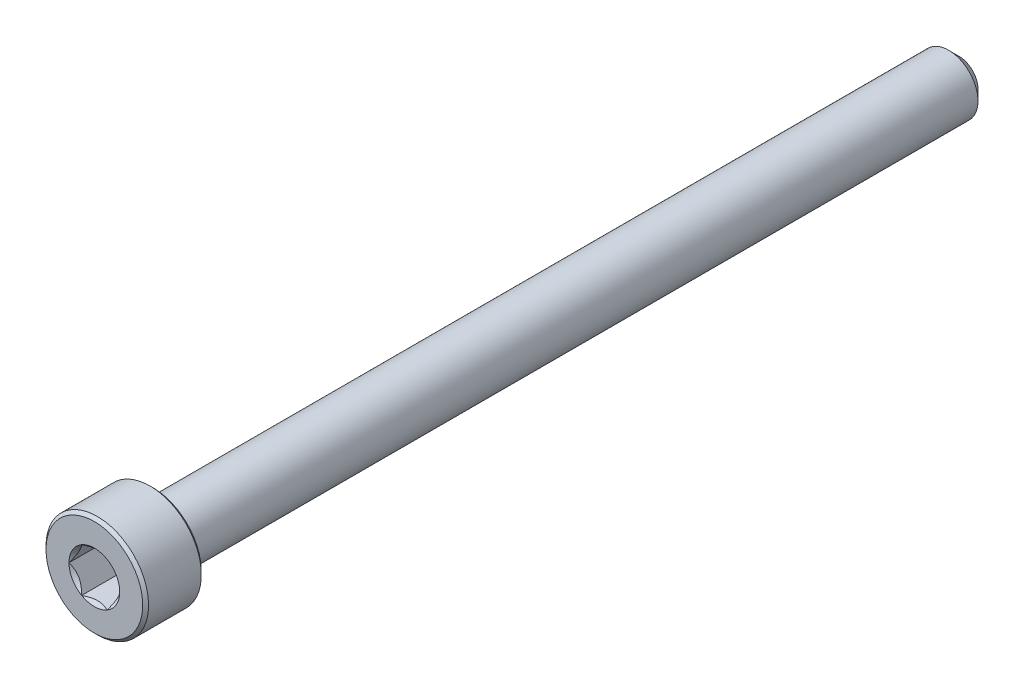
SolidWorks part; units mm, degrees
ref_plane "Front Plane" through (0, 0, 0) normal (0, 0, 1) x (1, 0, 0)
ref_plane "Top Plane" through (0, 0, 0) normal (0, 1, 0) x (1, 0, 0)
ref_plane "Right Plane" through (0, 0, 0) normal (1, 0, 0) x (0, 0, -1)
sketch "Sketch1" plane through (0, 0, 0) normal (1, 0, 0) x (0, 0, -1)
  line L0 (-29.5, 0) -> (29.5, 0) construction
  line L1 (29.5, 0) -> (29.5, 1.3) construction
  line L2 (29.5, 1.3) -> (28.8, 2) construction
  line L3 (28.8, 2) -> (9.5, 2) construction
  line L4 (9.5, 2) -> (-25.5, 2) construction
  line L5 (-25.5, 2) -> (-25.5, 3.5) construction
  line L6 (-25.5, 3.5) -> (-29.5, 3.5) construction
  line L7 (-29.5, 3.5) -> (-29.5, 0) construction
  line L8 (29.5, 1.3) -> (29.5, 2) construction
  line L9 (29.4563, 2.0758) -> (29.8063, 1.4696) construction
  line L10 (29.8063, 1.4696) -> (30.1563, 2.0758) construction
  line L11 (30.1563, 2.0758) -> (29.4563, 2.0758) construction
  line L12 (29.8063, 2.0758) -> (29.8063, 2) construction
  line L13 (29.8063, 1.4696) -> (29.8063, 1.5453) construction
  line L14 (29.7625, 1.5453) -> (29.85, 1.5453) construction
  line L15 (29.5, 2) -> (30.1125, 2) construction
  line L16 (29.4781, 2.0379) -> (30.1344, 2.0379) construction
  line L17 (29.5, 0) -> (29.5, -2) construction
  line L18 (-25.7, 3.5) -> (-25.5, 3.3) construction
  line L19 (-29.3, 3.5) -> (-29.5, 3.3) construction
  point P0 (-29.5, 1.5)
  point P3 (27.05, 2)
  point P4 (0, 0)
  point P18 (8.5, 2)
  point P22 (29.8063, 1.5453)
  point P24 (9.5, 2)
  point P25 (29.8063, 2)
  point P28 (29.8063, 2.0379)
  point P29 (27.05, -2)
  point P30 (-24.5, 2)
  point P31 (-27.5, 3.5)
  point P37 (-26.2, 3.5)
  point P38 (-29.2, 3.5)
  dimension "head height" = 4
  dimension "threaded length" = 20
  dimension "D1" = 45
  dimension "head dia" = 7
  dimension "thread dia" = 4
  dimension "drive size" = 3
  dimension "pitch" = 0.7
  dimension "D2" = 0.0875
  dimension "D3" = 0.7
  dimension "D4" = 2.45
  dimension "D5" = 1
  dimension "D6" = 1
  dimension "D7" = 0.2
  dimension "D8" = 0.2
  dimension "D9" = 0.2
  dimension "D10" = 0.1
  dimension "D11" = 0.5
  dimension "length" = 55
sketch "Sketch2" plane through (0, 0, 0) normal (1, 0, 0) x (0, 0, -1)
  line L0 (-29.5, 0) -> (-29.5, 3.3)
  line L1 (-29.3, 3.5) -> (-25.7, 3.5)
  line L2 (-25.5, 3.3) -> (-25.5, 2)
  line L3 (-25.5, 2) -> (28.8, 2)
  line L4 (28.8, 2) -> (29.5, 1.3)
  line L5 (29.5, 1.3) -> (29.5, 0)
  line L6 (-25.7, 3.5) -> (-25.5, 3.3) construction
  line L7 (29.5, 0) -> (-29.5, 0)
  line L8 (-29.3, 3.5) -> (-29.5, 3.3) construction
  line L9 (-25.7, 3.5) -> (-25.5, 3.3)
  line L10 (-29.3, 3.5) -> (-29.5, 3.3)
revolve "Revolve1" add sketch "Sketch2" angle 360 about L7
sketch "Sketch3" plane through (0, 0, 29.5) normal (0, 0, 1) x (1, 0, 0)
  line L1 (0.866, 1.5) -> (-0.866, 1.5)
  line L2 (-0.866, 1.5) -> (-1.7321, 0)
  line L3 (-1.7321, 0) -> (-0.866, -1.5)
  line L4 (-0.866, -1.5) -> (0.866, -1.5)
  line L5 (0.866, -1.5) -> (1.7321, 0)
  line L6 (1.7321, 0) -> (0.866, 1.5)
  circle A0 centre (0, 0) radius 1.5 construction
extrude "Cut-Extrude1" cut sketch "Sketch3" against normal offset from surface (3 mm away) 1 up to face at (-3.3, 0, 25.5)
sketch "Sketch4" plane through (0, 0, 29.5) normal (0, 0, 1) x (1, 0, 0)
  circle A0 centre (0, 0) radius 1.7321
extrude "Cut-Extrude2" cut sketch "Sketch4" against normal up to vertex (2 mm away) draft 45 up to point (0, 3.5, 27.5)
ref_plane "Plane1" [suppressed] through (0, 0, -9.5) normal (0, 0, 1) x (1, 0, 0)
split "Split1" [suppressed] bodies to split 106
sketch "Sketch6" [suppressed] plane through (0, 0, -29.5) normal (0, 0, -1) x (-1, 0, 0)
  circle A0 centre (0, 0) radius 2
curve "Helix/Spiral1" [suppressed] pitch 0.7 height 20.7 turns 29.5714
sketch "Sketch7" [suppressed] plane through (0, 0, 0) normal (1, 0, 0) x (0, 0, -1)
  line L0 (29.4781, 2.0379) -> (30.1344, 2.0379)
  line L1 (30.1344, 2.0379) -> (29.85, 1.5453)
  line L2 (29.85, 1.5453) -> (29.7625, 1.5453)
  line L3 (29.7625, 1.5453) -> (29.4781, 2.0379)
sweep "Cut-Sweep1" [suppressed] cut profiles "Sketch7" path "Helix/Spiral1"
sketch "Sketch8" [suppressed] plane through (0, 0, -9.5) normal (0, 0, -1) x (-1, 0, 0)
  circle A0 centre (0, 0) radius 2
extrude "Boss-Extrude1" [suppressed] add sketch "Sketch8" along normal through all draft 45
ref_plane "Plane2" [suppressed] through (0, 0, 27.5) normal (0, 0, 1) x (1, 0, 0)
sketch "Sketch9" [suppressed] plane through (0, 0, 27.5) normal (0, 0, 1) x (1, 0, 0)
  line L0 (0, 3.325) -> (0.0611, 3.4995)
  line L1 (0, 3.325) -> (-0.0611, 3.4995)
  line L2 (0, 3.5) -> (0, 0) construction
  line L3 (-0.0611, 3.4995) -> (0, 0) construction
  line L4 (0, 0) -> (0.0611, 3.4995) construction
  arc A0 (0.0611, 3.4995) -> (-0.0611, 3.4995) centre (0, 0) ccw
  circle A1 centre (0, 0) radius 3.325 construction
  dimension "D2" = 6.65
  dimension "D3" = 2
extrude "Cut-Extrude4" [suppressed] cut sketch "Sketch9" against normal up to vertex and the other way up to vertex
pattern_circular "CirPattern2" [suppressed] count 175 over 360 about axis through (0, 0, 29.5) along (0, 0, -1) of bodies 113
equation "\"D2@Sketch1\"=\"pitch@Sketch1\"/8"
equation "\"D3@Sketch1\"=\"pitch@Sketch1\""
equation "\"D3@Helix/Spiral1\"=\"threaded length@Sketch1\"+\"pitch@Sketch1\""
equation "\"D4@Helix/Spiral1\"=\"pitch@Sketch1\""
equation "\"D4@Sketch1\"=\"pitch@Sketch1\"*3.5"
equation "\"D7@Sketch1\"=\"head height@Sketch1\"*.05"
equation "\"D8@Sketch1\"=\"D7@Sketch1\""
equation "\"D9@Sketch1\"=\"D7@Sketch1\""
equation "\"D10@Sketch1\"=\"D7@Sketch1\"/2"
equation "\"D11@Sketch1\"=\"D10@Sketch1\"*5"
equation "\"D2@Sketch9\"=\"D1@Sketch9\"*.95"
equation "\"D1@CirPattern2\"= ( 360 / \"D3@Sketch9\" ) - 5"
